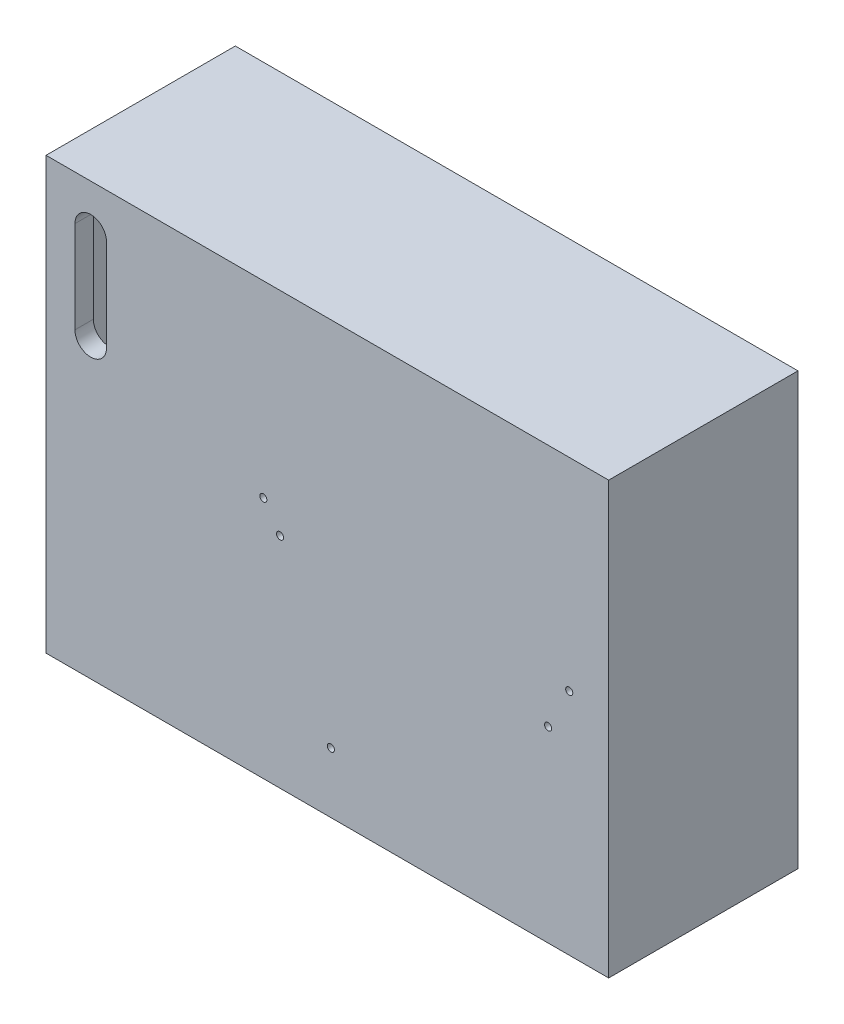
SolidWorks part; units mm, degrees
ref_plane "Front Plane" through (0, 0, 0) normal (0, 0, 1) x (1, 0, 0)
ref_plane "Top Plane" through (0, 0, 0) normal (0, 1, 0) x (1, 0, 0)
ref_plane "Right Plane" through (0, 0, 0) normal (1, 0, 0) x (0, 0, -1)
sketch "SKELETON" plane through (0, 0, 0) normal (0, 0, 1) x (1, 0, 0)
  line L0 (-7, 157) -> (207, 157)
  line L1 (0, 0) -> (200, 0)
  line L2 (0, 0) -> (0, 150)
  line L3 (0, 150) -> (200, 150)
  line L4 (200, 0) -> (200, 150)
  line L5 (207, -7) -> (207, 157)
  line L6 (-7, -7) -> (207, -7)
  line L7 (-7, -7) -> (-7, 157)
  circle A0 centre (192, 80) radius 1.35
  circle A1 centre (82.0025, 76.1895) radius 1.35
  circle A2 centre (75.6471, 85.4852) radius 1.35
  arc A3 (185.5204, 64.2828) -> (182.3962, 64.2828) centre (183.9583, 64.2828) ccw construction
  arc A4 (182.3962, 64.2828) -> (185.5204, 64.2828) centre (183.9583, 64.2828) ccw construction
  arc A5 (185.5204, 64.2828) -> (182.3962, 64.2828) centre (183.9583, 64.2828) ccw construction
  arc A6 (182.3962, 64.2828) -> (185.5204, 64.2828) centre (183.9583, 64.2828) ccw construction
  circle A7 centre (183.9583, 64.2828) radius 1.35
  arc A8 (102.8942, 15.9466) -> (99.77, 15.9466) centre (101.3321, 15.9466) ccw construction
  arc A9 (99.77, 15.9466) -> (102.8942, 15.9466) centre (101.3321, 15.9466) ccw construction
  arc A10 (102.8942, 15.9466) -> (99.77, 15.9466) centre (101.3321, 15.9466) ccw construction
  arc A11 (99.77, 15.9466) -> (102.8942, 15.9466) centre (101.3321, 15.9466) ccw construction
  circle A12 centre (101.3321, 15.9466) radius 1.35
  dimension "D4" = 2.7
  dimension "D7" = 2.7
  dimension "D8" = 2.7
  dimension "D2" = 200
  dimension "D3" = 150
  dimension "D5" = 70
  dimension "D6" = 8
  dimension "D1" = 7
extrude "Boss-Extrude1" add sketch "SKELETON" along normal blind 7 contours L1 L4 L3 L2 | L7 L6 L5 L0 L4 L1 L2 L3 region at (100, 154.3039, 0) region at (99.9742, 75.0101, 0)
extrude "Boss-Extrude2" add sketch "SKELETON<3>" against normal blind 65 contours L7 L6 L5 L0 L4 L1 L2 L3 region at (100, 154.3039, 0)
sketch "SKELETON<3>" plane through (0, 0, 0) normal (0, 0, 1) x (1, 0, 0) same geometry as "SKELETON"
sketch "Sketch3" plane through (0, 0, 0) normal (0, 0, -1) x (-1, 0, 0)
  line L0 (-10, 140) -> (-10, 105) construction
  line L1 (-4, 140) -> (-4, 105)
  line L2 (-16, 140) -> (-16, 105)
  line L3 (0, 0) -> (0, 150) construction
  line L4 (0, 150) -> (-200, 150) construction
  arc A0 (-4, 140) -> (-16, 140) centre (-10, 140) ccw
  arc A1 (-16, 105) -> (-4, 105) centre (-10, 105) ccw
  point P2 (-10, 122.5)
  dimension "D2" = 6
  dimension "D1" = 35
  dimension "D3" = 10
  dimension "D4" = 10
extrude "Cut-Extrude1" cut sketch "Sketch3" against normal blind 9
